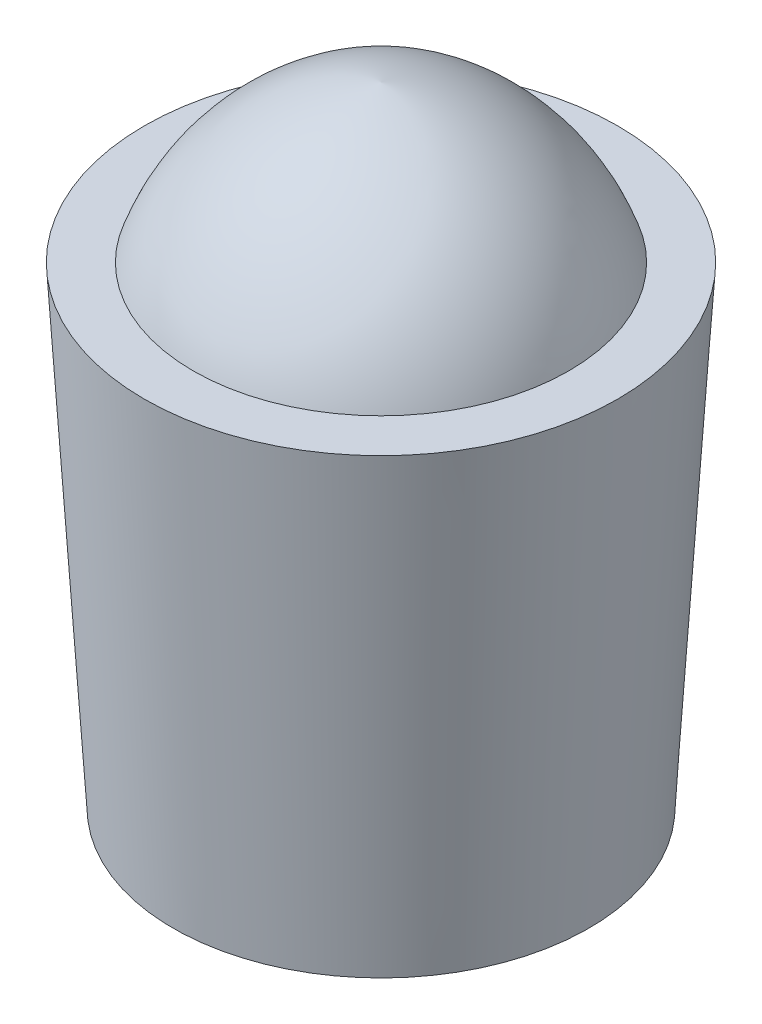
SolidWorks part; units mm, degrees
material "Nylon 101"
ref_plane "Front" through (0, 0, 0) normal (0, 0, 1) x (1, 0, 0)
ref_plane "Top" through (0, 0, 0) normal (0, 1, 0) x (1, 0, 0)
ref_plane "Right" through (0, 0, 0) normal (1, 0, 0) x (0, 0, -1)
ref_axis "Axis1" through (0, 0, 55) along (0, 0, -1)
sketch "Sketch1" plane through (0, 0, 0) normal (0, 0, 1) x (1, 0, 0)
  line L0 (0, 0) -> (0, 19.2117)
  line L1 (0, 0) -> (6.35, 0)
  line L2 (6.35, 0) -> (7.2319, 14.4436)
  line L3 (7.2319, 14.4436) -> (5.7391, 14.4436)
  arc A0 (0, 19.2117) -> (5.7391, 14.4436) centre (-1.0088, 12.1594) cw
  point P5 (6.35, 0)
  point P8 (0, 18.3159)
  point P9 (5.7391, 14.4169)
  point P10 (0, 0)
  point P11 (0.9237, 18.8903)
  point P12 (0, 19.2117)
  point P13 (0.0469, 19.2117)
  dimension "D2" = 7.124
  dimension "D1" = 6.35
  dimension "D3" = 5.7391
  dimension "D4" = 7.2319
  dimension "D5" = 1.0088
  dimension "D6" = 12.1594
revolve "Revolve1" add sketch "Sketch1" angle 360 about L0
